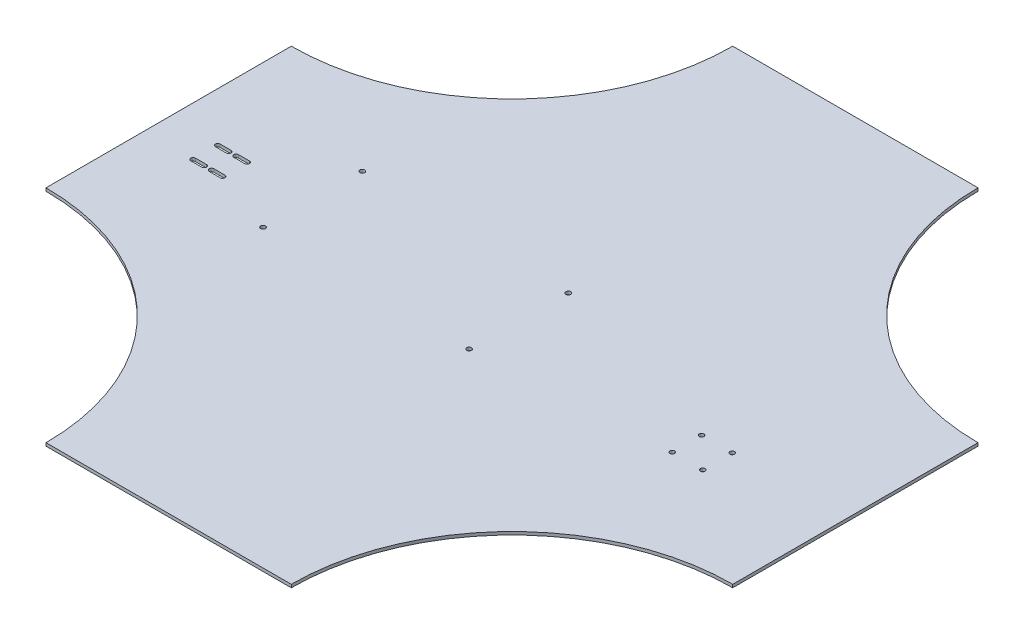
SolidWorks part; units mm, degrees
material "6061 Alloy"
ref_plane "Front Plane" through (0, 0, 0) normal (0, 0, 1) x (1, 0, 0)
ref_plane "Top Plane" through (0, 0, 0) normal (0, 1, 0) x (1, 0, 0)
ref_plane "Right Plane" through (0, 0, 0) normal (1, 0, 0) x (0, 0, -1)
sketch "Sketch1" plane through (0, 0, 0) normal (0, 1, 0) x (1, 0, 0)
  line L9 (-127, -355.6) -> (127, -355.6)
  line L10 (-355.6, -127) -> (-355.6, 127)
  line L11 (-127, 355.6) -> (127, 355.6)
  line L12 (355.6, -127) -> (355.6, 127)
  line L13 (-193.9554, -193.9554) -> (193.9554, 193.9554) construction
  line L14 (-193.9554, 193.9554) -> (193.9554, -193.9554) construction
  arc A8 (-355.6, 127) -> (-127, 355.6) centre (-355.6, 355.6) ccw
  arc A9 (127, 355.6) -> (355.6, 127) centre (355.6, 355.6) ccw
  arc A10 (355.6, -127) -> (127, -355.6) centre (355.6, -355.6) ccw
  arc A11 (-127, -355.6) -> (-355.6, -127) centre (-355.6, -355.6) ccw
  point P0 (0, 0)
  point P1 (0, 0)
  point P2 (0, 0)
  dimension "D3" = 457.2
  dimension "D4" = 457.2
  dimension "D5" = 457.2
  dimension "D6" = 457.2
  dimension "D1" = 711.2
  dimension "D2" = 711.2
extrude "Boss-Extrude1" add sketch "Sketch1" along normal blind 3.175
sketch "Sketch2" plane through (0, 3.175, 0) normal (0, 1, 0) x (1, 0, 0)
  line L0 (-304.8, 2.413) -> (-293.37, 2.413)
  line L1 (-304.8, -22.987) -> (-293.37, -22.987)
  line L2 (-293.37, -2.413) -> (-304.8, -2.413)
  line L3 (-285.75, -2.413) -> (-274.32, -2.413)
  line L4 (-285.75, -22.987) -> (-274.32, -22.987)
  line L5 (-274.32, 2.413) -> (-285.75, 2.413)
  line L6 (-293.37, -27.813) -> (-304.8, -27.813)
  line L7 (-355.6, 127) -> (-355.6, -127) construction
  line L8 (-274.32, -27.813) -> (-285.75, -27.813)
  arc A0 (-293.37, -2.413) -> (-293.37, 2.413) centre (-293.37, 0) ccw
  arc A1 (-274.32, -2.413) -> (-274.32, 2.413) centre (-274.32, 0) ccw
  arc A2 (-274.32, -27.813) -> (-274.32, -22.987) centre (-274.32, -25.4) ccw
  arc A3 (-293.37, -27.813) -> (-293.37, -22.987) centre (-293.37, -25.4) ccw
  arc A4 (-285.75, 2.413) -> (-285.75, -2.413) centre (-285.75, 0) ccw
  arc A5 (-304.8, 2.413) -> (-304.8, -2.413) centre (-304.8, 0) ccw
  arc A6 (-304.8, -22.987) -> (-304.8, -27.813) centre (-304.8, -25.4) ccw
  arc A7 (-285.75, -22.987) -> (-285.75, -27.813) centre (-285.75, -25.4) ccw
  dimension "D1" = 4.826
  dimension "D2" = 4.826
  dimension "D3" = 4.826
  dimension "D4" = 4.826
  dimension "D5" = 4.826
  dimension "D6" = 4.826
  dimension "D7" = 4.826
  dimension "D8" = 4.826
  dimension "D9" = 11.43
  dimension "D10" = 11.43
  dimension "D11" = 11.43
  dimension "D12" = 11.43
  dimension "D13" = 19.05
  dimension "D14" = 19.05
  dimension "D15" = 25.4
  dimension "D16" = 25.4
  dimension "D17" = 0
  dimension "D18" = 50.8
extrude "Cut-Extrude1" cut sketch "Sketch2" against normal through all both and the other way through all
sketch "Sketch4" plane through (0, 3.175, 0) normal (0, 1, 0) x (1, 0, 0)
  circle A0 centre (237.49, -9.4302) radius 2.413
  circle A1 centre (205.74, -9.4302) radius 2.413
  circle A2 centre (237.49, -39.9102) radius 2.413
  circle A3 centre (205.74, -39.9102) radius 2.413
extrude "Cut-Extrude2" cut sketch "Sketch4" against normal through all
sketch "Sketch5" plane through (0, 0, 0) normal (0, -1, 0) x (1, 0, 0)
  circle A0 centre (-207.7901, 50.0166) radius 2.5
  circle A1 centre (-206.624, -51.5767) radius 2.5
  circle A2 centre (8.0956, 52.4945) radius 2.478
  circle A3 centre (9.2617, -49.0988) radius 2.5
extrude "Cut-Extrude3" cut sketch "Sketch5" against normal through all
